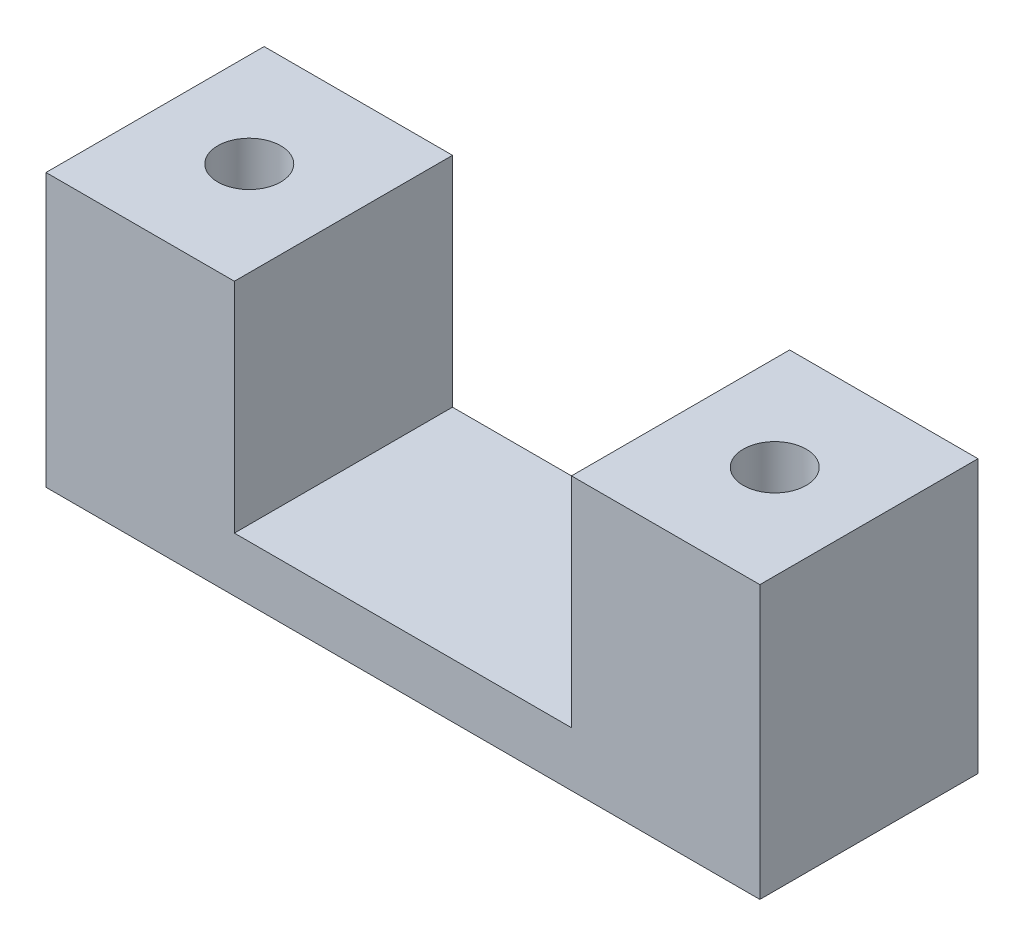
SolidWorks part; units mm, degrees
ref_plane "Front Plane" through (0, 0, 0) normal (0, 0, 1) x (1, 0, 0)
ref_plane "Top Plane" through (0, 0, 0) normal (0, 1, 0) x (1, 0, 0)
ref_plane "Right Plane" through (0, 0, 0) normal (1, 0, 0) x (0, 0, -1)
sketch "Sketch1" plane through (0, 0, 0) normal (0, 1, 0) x (1, 0, 0)
  line L1 (0, 0) -> (72, 0)
  line L2 (0, 0) -> (0, 22)
  line L3 (0, 22) -> (72, 22)
  line L4 (72, 0) -> (72, 22)
  line L7 (30.2143, -18.8036) -> (29.5714, -18.8036)
  dimension "D1" = 72
  dimension "D2" = 22
extrude "Boss-Extrude1" add sketch "Sketch1" along normal blind 27.5 contours L1 L4 L3 L2 region at (36, 0, -11)
sketch "Sketch2" plane through (0, 27.5, 0) normal (0, 1, 0) x (1, 0, 0)
  line L0 (0, 0) -> (72, 0) construction
  line L1 (19, 22) -> (53, 22)
  line L2 (19, 22) -> (19, 0)
  line L3 (19, 0) -> (53, 0)
  line L4 (53, 22) -> (53, 0)
  line L5 (19, 22) -> (53, 0) construction
  line L6 (19, 0) -> (53, 22) construction
  line L7 (36, 0) -> (36, 11) construction
  point P0 (36, 11)
  dimension "D1" = 34
  dimension "D2" = 22
extrude "Cut-Extrude1" cut sketch "Sketch2" against normal blind 22
sketch "Sketch3" plane through (0, 27.5, 0) normal (0, 1, 0) x (1, 0, 0)
  line L0 (36, 22) -> (36, 0) construction
  line L1 (53, 22) -> (19, 22) construction
  line L2 (19, 0) -> (53, 0) construction
  line L3 (19, 22) -> (19, 0) construction
  circle A0 centre (9.5, 11) radius 3.175
  circle A1 centre (62.5, 11) radius 3.175
  dimension "D1" = 6.35
  dimension "D2" = 9.5
extrude "Cut-Extrude2" cut sketch "Sketch3" against normal blind 69
sketch "Sketch5" plane through (0, 0, 0) normal (0, -1, 0) x (1, 0, 0)
  line L0 (36, 0) -> (36, -22) construction
  line L1 (0, 0) -> (72, 0) construction
  line L2 (0, -22) -> (72, -22) construction
  circle A0 centre (9.5, -11) radius 5.5
  circle A1 centre (62.5, -11) radius 5.5
  dimension "D1" = 11
extrude "Cut-Extrude3" cut sketch "Sketch5" against normal blind 5.5
